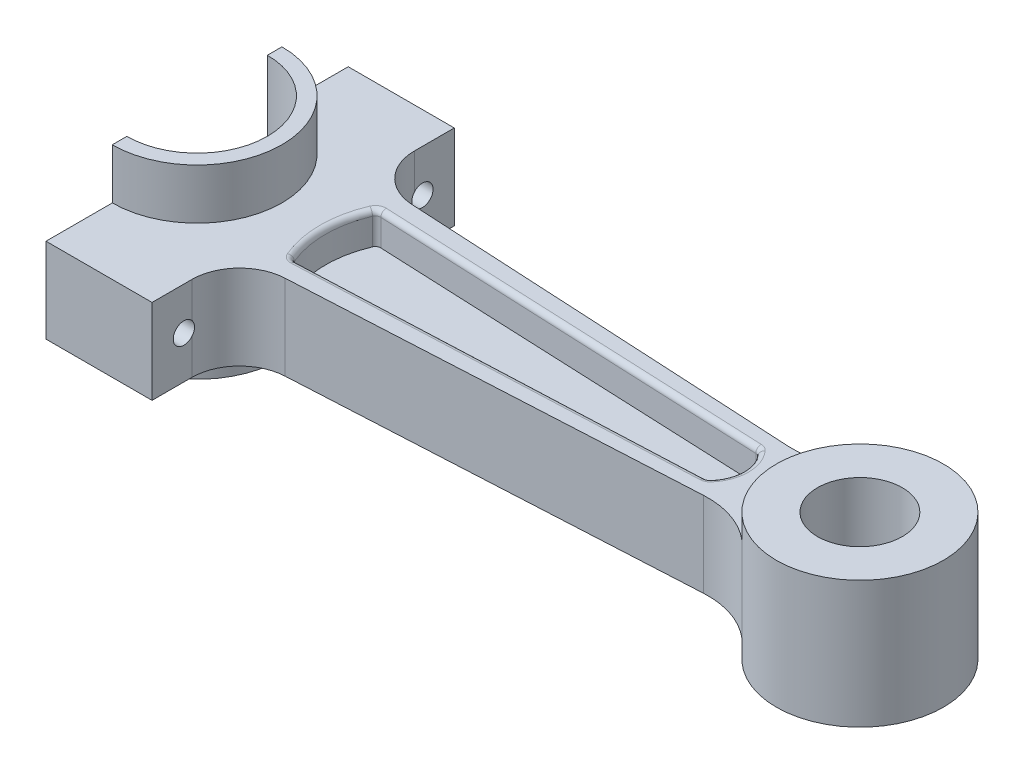
SolidWorks part; units mm, degrees
ref_plane "Front Plane" through (0, 0, 0) normal (0, 0, 1) x (1, 0, 0)
ref_plane "Top Plane" through (0, 0, 0) normal (0, 1, 0) x (1, 0, 0)
ref_plane "Right Plane" through (0, 0, 0) normal (1, 0, 0) x (0, 0, -1)
sketch "Sketch1" plane through (0, 0, 0) normal (0, 1, 0) x (1, 0, 0)
  line L0 (-19.7748, 0) -> (230.2252, 0) construction
  line L1 (0, 60.9146) -> (0, -74.0229) construction
  line L2 (-19.7748, 26.5) -> (-19.7748, 56.9968)
  line L3 (-19.7748, 56.9968) -> (20.2252, 56.9968)
  line L4 (20.2252, 56.9968) -> (20.2252, 41.9968)
  line L5 (37.2877, 24) -> (187.2877, 16)
  line L6 (37.2877, -24) -> (187.2877, -16)
  line L7 (20.2252, -56.9968) -> (20.2252, -41.9968)
  line L8 (-19.7748, -56.9968) -> (20.2252, -56.9968)
  line L9 (-19.7748, -26.5) -> (-19.7748, -56.9968)
  arc A0 (-19.7748, -26.5) -> (-19.7748, 26.5) centre (-19.7748, 0) ccw
  circle A1 centre (230.2252, 0) radius 16
  circle A2 centre (230.2252, 0) radius 31.5
  arc A3 (20.2252, 41.9968) -> (37.2877, 24) centre (38.2475, 41.9968) ccw
  arc A4 (187.2877, 16) -> (209.449, 23.677) centre (188.9435, 47.0455) ccw
  arc A5 (187.2877, -16) -> (209.449, -23.677) centre (188.9435, -47.0455) cw
  arc A6 (20.2252, -41.9968) -> (37.2877, -24) centre (38.2475, -41.9968) cw
  arc A7 (-19.7748, -32) -> (-19.7748, 32) centre (-19.7748, 0) ccw
  point P5 (112.2877, 20)
  dimension "D2" = 26.5
  dimension "D6" = 32
  dimension "D7" = 63
  dimension "D8" = 24
  dimension "D10" = 32
  dimension "D1" = 250
  dimension "D3" = 30.4968
  dimension "D4" = 40
  dimension "D5" = 15
  dimension "D9" = 16
  dimension "D11" = 150
  dimension "D12" = 20
extrude "Boss-Extrude1" add sketch "Sketch1" along normal mid plane 32 contours A7 L9 L8 L7 A6 L6 A5 A2 A4 L5 A3 L4 L3 L2 region at (74.3075, 0, 0)
extrude "Boss-Extrude2" add sketch "Sketch1<5>" along normal mid plane 48 contours A2 A1 region at (242.8537, 0, -27.8825)
sketch "Sketch1<5>" plane through (0, 0, 0) normal (0, 1, 0) x (1, 0, 0) same geometry as "Sketch1"
extrude "Boss-Extrude3" add sketch "Sketch1<6>" along normal mid plane 70 contours L9 A7 L2 A0 region at (-19.0593, 0, -29.25)
sketch "Sketch1<6>" plane through (0, 0, 0) normal (0, 1, 0) x (1, 0, 0) same geometry as "Sketch1"
sketch "Sketch4" plane through (0, 16, 0) normal (0, 1, 0) x (1, 0, 0)
  line L0 (20.2252, 56.9968) -> (20.2252, 41.9968) construction
  line L2 (32.2252, -16.0019) -> (182.2252, -9.5019)
  line L3 (32.2252, 16.0019) -> (182.2252, 9.5019)
  arc A0 (182.2252, -9.5019) -> (182.2252, 9.5019) centre (172.7233, 0) ccw
  arc A1 (32.2252, -16.0019) -> (32.2252, 16.0019) centre (66.4109, 0) cw
  dimension "D1" = 150
  dimension "D2" = 12
extrude "Cut-Extrude1" cut sketch "Sketch4" against normal blind 12
fillet "Fillet1" radius 2 8 edges at (32.2252, 10, -16.0019) (182.2252, 10, -9.5019) (32.2252, 10, 16.0019) (182.2252, 10, 9.5019) (28.6654, 16, 0) (107.2252, 16, -12.7519) (186.161, 16, 0) (107.2252, 16, 12.7519)
mirror "Mirror5" about plane through (0, 0, 0) normal (0, 1, 0) of "Cut-Extrude1"
fillet "Fillet3" radius 2 8 edges at (186.161, -16, 0) (107.2252, -16, 12.7519) (28.6654, -16, 0) (107.2252, -16, -12.7519) (32.2252, -10, 16.0019) (32.2252, -10, -16.0019) (182.2252, -10, -9.5019) (182.2252, -10, 9.5019)
sketch "Sketch6" plane through (-19.7748, 0, 0) normal (-1, 0, 0) x (0, 0, 1)
  line L0 (0, 0) -> (-65.6954, 0) construction
  line L1 (0, 21.7124) -> (0, -25.6826) construction
  circle A0 centre (-45, 0) radius 4
  circle A1 centre (45, 0) radius 4
  dimension "D1" = 8
  dimension "D2" = 45
extrude "Cut-Extrude4" cut sketch "Sketch6" against normal through all
sketch "Sketch5" plane through (-19.7748, 0, 0) normal (-1, 0, 0) x (0, 0, 1)
  line L0 (0, 0) -> (-56.9968, 0) construction
  line L1 (-56.9968, 16) -> (-56.9968, -16) construction
  circle A0 centre (-45, 0) radius 4
  dimension "D1" = 8
  dimension "D2" = 45
